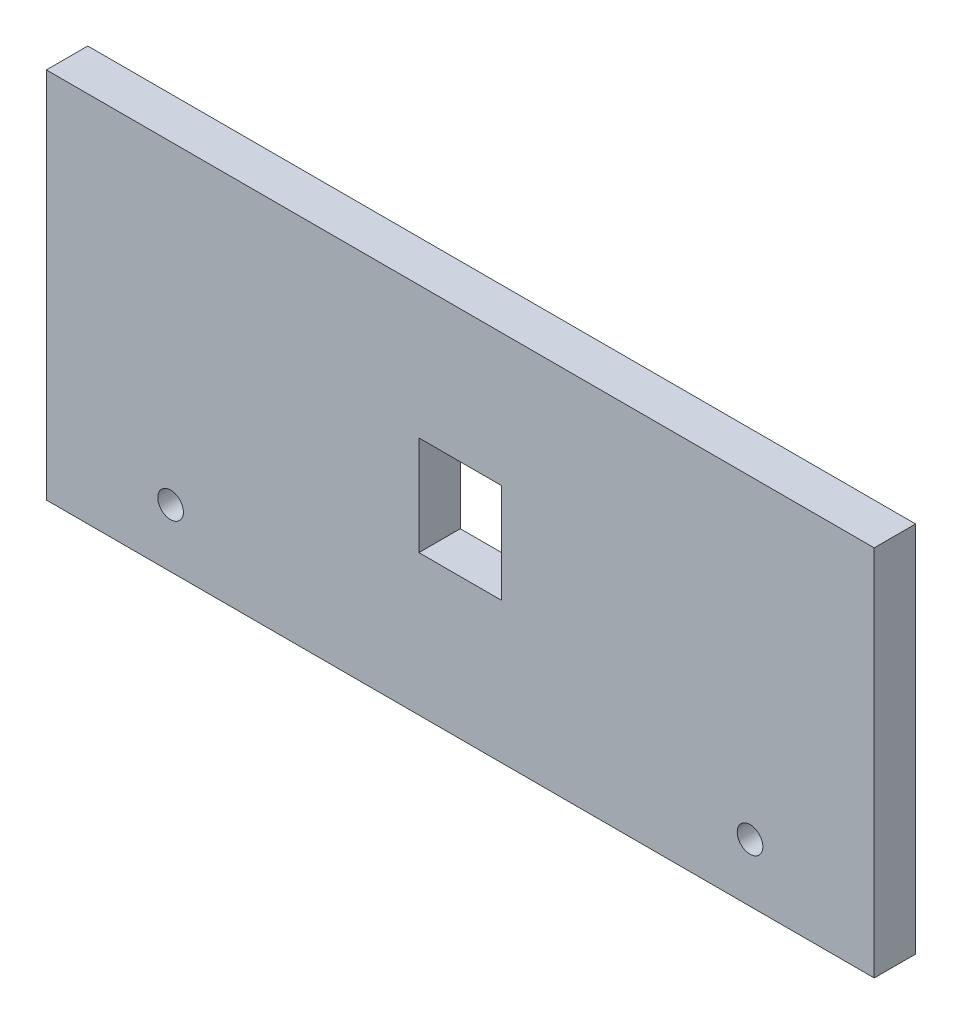
SolidWorks part; units mm, degrees
ref_plane "Plan de face" through (0, 0, 0) normal (0, 0, 1) x (1, 0, 0)
ref_plane "Plan de dessus" through (0, 0, 0) normal (0, 1, 0) x (1, 0, 0)
ref_plane "Plan de droite" through (0, 0, 0) normal (1, 0, 0) x (0, 0, -1)
sketch "Esquisse1" plane through (0, 0, 0) normal (0, 0, 1) x (1, 0, 0)
  line L0 (0, 0) -> (28.085, 0) construction
  line L1 (-50, -22.5) -> (50, -22.5)
  line L2 (-50, -22.5) -> (-50, 22.5)
  line L3 (-50, 22.5) -> (50, 22.5)
  line L4 (50, -22.5) -> (50, 22.5)
  line L5 (-50, -22.5) -> (50, 22.5) construction
  line L6 (-50, 22.5) -> (50, -22.5) construction
  line L7 (0, 0) -> (0, 14.2531) construction
  line L8 (0, 0) -> (0, 0.5) construction
  line L13 (-5, -5.5) -> (5, -5.5)
  line L14 (-5, -5.5) -> (-5, 6.5)
  line L15 (-5, 6.5) -> (5, 6.5)
  line L16 (5, -5.5) -> (5, 6.5)
  line L17 (-5, -5.5) -> (5, 6.5) construction
  line L18 (-5, 6.5) -> (5, -5.5) construction
  circle A0 centre (-35, -15.5) radius 1.55
  circle A1 centre (35, -15.5) radius 1.55
  point P0 (0, 0)
  point P15 (0, 0)
  point P17 (0.8333, 1.5)
  point P25 (0, 0)
  point P27 (-33.9395, -15.2728)
  dimension "D3" = 3.1
  dimension "D5" = 15
  dimension "D1" = 100
  dimension "D2" = 45
  dimension "D4" = 23
  dimension "D6" = 10
  dimension "D7" = 12
  dimension "D8" = 7
extrude "Boss.-Extru.1" add sketch "Esquisse1" against normal blind 5
